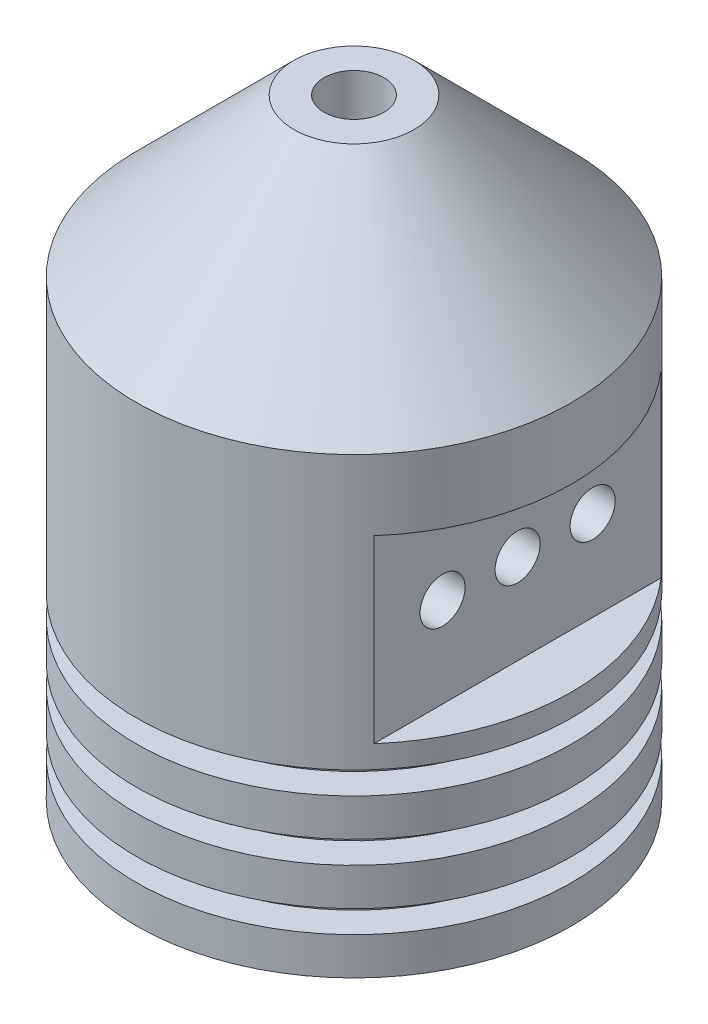
SolidWorks part; units mm, degrees
material "铜"
ref_plane "前视基准面" through (0, 0, 0) normal (0, 0, 1) x (1, 0, 0)
ref_plane "上视基准面" through (0, 0, 0) normal (0, 1, 0) x (1, 0, 0)
ref_plane "右视基准面" through (0, 0, 0) normal (1, 0, 0) x (0, 0, -1)
sketch "草图1" plane through (0, 0, 0) normal (0, 1, 0) x (1, 0, 0)
  circle A0 centre (0, 0) radius 14.5
  dimension "D1" = 29
extrude "凸台-拉伸1" add sketch "草图1" along normal blind 41.7
chamfer "倒角1" distance 10.5 angle 45 1 edges at (0, 41.7, 14.5)
sketch "草图2" plane through (0, 41.7, 0) normal (0, 1, 0) x (1, 0, 0)
  circle A0 centre (0, 0) radius 2
  dimension "D1" = 4
extrude "切除-拉伸1" cut sketch "草图2" against normal through all
chamfer "倒角2" distance 5 distance2 1 1 edges at (0, 0, 14.5) first distance on face at (0, 0, 2)
sketch "草图3" plane through (0, 0, 0) normal (0, 0, 1) x (1, 0, 0)
  line L0 (14.5, 1) -> (14.5, 31.2) construction
  line L1 (12.5, 5) -> (14.5, 5)
  line L2 (12.5, 5) -> (12.5, 3.5)
  line L3 (12.5, 3.5) -> (14.5, 3.5)
  line L4 (14.5, 5) -> (14.5, 3.5)
  line L5 (14.5, 1) -> (-14.5, 1) construction
  line L6 (12.5, 9) -> (14.5, 9)
  line L7 (12.5, 9) -> (12.5, 7.5)
  line L8 (12.5, 7.5) -> (14.5, 7.5)
  line L9 (14.5, 9) -> (14.5, 7.5)
  line L10 (12.5, 13) -> (14.5, 13)
  line L11 (12.5, 13) -> (12.5, 11.5)
  line L12 (12.5, 11.5) -> (14.5, 11.5)
  line L13 (14.5, 13) -> (14.5, 11.5)
  line L14 (0, 0) -> (0, 41.7) construction
  line L15 (2, 41.7) -> (-2, 41.7) construction
  dimension "D1" = 2.5
  dimension "D2" = 2.5
  dimension "D3" = 1.5
  dimension "D4" = 2
  dimension "D5" = 2.5
revolve "切除-旋转1" cut sketch "草图3" angle 360 about L14
sketch "草图5" plane through (0, 0, 0) normal (0, 0, 1) x (1, 0, 0)
  line L0 (14.5, 1) -> (-14.5, 1) construction
  line L1 (10.9, 26.5) -> (17.8793, 26.5)
  line L2 (10.9, 26.5) -> (10.9, 14.5)
  line L3 (10.9, 14.5) -> (17.8793, 14.5)
  line L4 (17.8793, 26.5) -> (17.8793, 14.5)
  line L5 (-14.5, 31.2) -> (-14.5, 13) construction
  dimension "D1" = 12
  dimension "D2" = 13.5
  dimension "D3" = 12
  dimension "D4" = 25.4
extrude "切除-拉伸2" cut sketch "草图5" against normal through all both and the other way through all
sketch "草图6" plane through (0, 0, 0) normal (0, -1, 0) x (1, 0, 0)
  circle A0 centre (0, 0) radius 8.65
  dimension "D1" = 17.3
extrude "切除-拉伸3" cut sketch "草图6" against normal blind 5.6
chamfer "倒角3" distance 0.5 angle 45 1 edges at (0, 0, -8.65)
sketch "草图7" plane through (0, 0, 0) normal (0, -1, 0) x (1, 0, 0)
  circle A0 centre (0, 0) radius 8.15
  dimension "D1" = 16.3
extrude "切除-拉伸4" cut sketch "草图7" against normal blind 15.6
chamfer "倒角4" distance 0.5 angle 45 1 edges at (0, 5.6, -8.15)
sketch "草图8" plane through (0, 0, 0) normal (0, -1, 0) x (1, 0, 0)
  circle A0 centre (0, 0) radius 7
  dimension "D1" = 14
extrude "切除-拉伸5" cut sketch "草图8" against normal blind 17.5
sketch "草图9" plane through (10.9, 0, 0) normal (1, 0, 0) x (0, 0, -1)
  line L0 (-9.5624, 20.5) -> (9.5624, 20.5) construction
  line L1 (-9.5624, 14.5) -> (-9.5624, 26.5) construction
  line L2 (9.5624, 26.5) -> (9.5624, 14.5) construction
  circle A0 centre (0, 20.5) radius 1.5
  circle A1 centre (-5, 20.5) radius 1.5
  circle A2 centre (5, 20.5) radius 1.5
  dimension "D1" = 3
  dimension "D2" = 10
  dimension "D3" = 5
extrude "切除-拉伸6" cut sketch "草图9" against normal blind 8 contours A1 L0 | L0 A1 | A2 L0 | L0 A2 region at (10.9, 21.1366, 5) region at (10.9, 21.1366, -5) region at (10.9, 19.8634, -5) region at (10.9, 19.8634, 5)
extrude "切除-拉伸7" cut sketch "草图9<3>" against normal blind 8 contours A0 L0 | L0 A0 region at (10.9, 21.1366, 0) region at (10.9, 19.8634, 0)
sketch "草图9<3>" plane through (10.9, 0, 0) normal (1, 0, 0) x (0, 0, -1) same geometry as "草图9"
sketch "草图10" plane through (0, 17.5, 0) normal (0, -1, 0) x (1, 0, 0)
  circle A0 centre (4.5, 0) radius 1.5
  dimension "D1" = 3
  dimension "D2" = 4.5
extrude "切除-拉伸8" cut sketch "草图10" against normal blind 7
